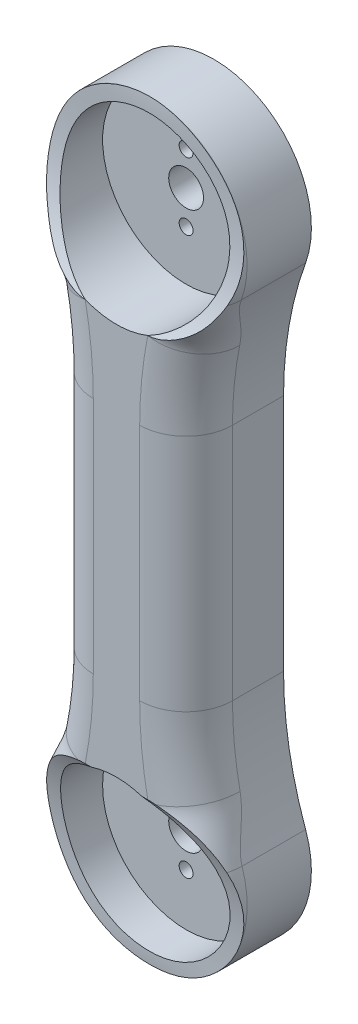
SolidWorks part; units mm, degrees
ref_plane "Front Plane" through (0, 0, 0) normal (0, 0, 1) x (1, 0, 0)
ref_plane "Top Plane" through (0, 0, 0) normal (0, 1, 0) x (1, 0, 0)
ref_plane "Right Plane" through (0, 0, 0) normal (1, 0, 0) x (0, 0, -1)
sketch "Sketch9" plane through (0, 0, 0) normal (0, 0, 1) x (1, 0, 0)
  line L0 (-9.4143, 0.3919) -> (-9.4143, 5.0677) construction
  line L1 (-28.6016, 137.3176) -> (-28.5046, 137.3176) construction
  line L2 (-24.4143, 111.7748) -> (-24.4143, 60.3605)
  line L3 (5.5857, 111.7748) -> (5.5857, 60.3605)
  circle A0 centre (-9.4143, 153.3177) radius 1.5
  circle A1 centre (-9.4143, 146.0677) radius 3.7501
  circle A2 centre (-9.4143, 138.8176) radius 1.5
  arc A3 (10.3381, 138.9375) -> (-29.1668, 138.9375) centre (-9.4143, 146.0677) ccw
  circle A4 centre (-9.4143, 18.8177) radius 1.5
  circle A5 centre (-9.4143, 26.0677) radius 3.7501
  circle A6 centre (-9.4143, 33.3177) radius 1.5
  arc A7 (10.3381, 33.1979) -> (-29.1668, 33.1979) centre (-9.4143, 26.0677) cw
  arc A8 (-29.1668, 33.1979) -> (-24.4143, 60.3605) centre (-104.4143, 60.3605) ccw
  arc A9 (5.5857, 60.3605) -> (10.3381, 33.1979) centre (85.5857, 60.3605) ccw
  arc A10 (5.5857, 111.7748) -> (10.3381, 138.9375) centre (85.5857, 111.7748) cw
  arc A11 (-29.1668, 138.9375) -> (-24.4143, 111.7748) centre (-104.4143, 111.7748) cw
  point P13 (-9.4143, 86.0677)
  point P14 (-9.4143, 86.9252)
extrude "Boss-Extrude2" add sketch "Sketch9" along normal blind 21 separate body
sketch "Sketch12" plane through (0, 0, 21) normal (0, 0, 1) x (1, 0, 0)
  line L0 (120.7444, 166.8402) -> (120.7444, 163.8342) construction
  line L1 (-24.895, 85.8401) -> (5.105, 85.8401) construction
  line L2 (-9.4143, 149.8177) -> (-9.4143, 142.3176) construction
  circle A0 centre (-9.4143, 146.0677) radius 17.994
  circle A1 centre (-9.4143, 25.6126) radius 17.994
  circle A2 centre (-9.4143, 146.0677) radius 3.7501 construction
extrude "Cut-Extrude6" cut sketch "Sketch12" against normal blind 15
fillet "Fillet2" radius 10 6 edges at (-25.6114, 125.5625, 21) (6.7827, 125.5625, 21) (5.5857, 86.0677, 21) (6.7827, 46.5729, 21) (-25.6114, 46.5729, 21) (-24.4143, 86.0677, 21)
sketch "Sketch14" plane through (0, 0, 0) normal (1, 0, 0) x (0, 0, -1)
  line L0 (-21, 8.0737) -> (-21, 7.6186)
  line L1 (-14.3283, 5.0677) -> (-13.8527, 5.0677)
  line L6 (-21, 164.0617) -> (-21, 139.9581) construction
  line L7 (-21, 164.0617) -> (-21, 139.9581)
  line L8 (-21, 129.3834) -> (-21, 139.9581) construction
  line L10 (-21, 129.3834) -> (-21, 139.9581)
  line L11 (-21, 42.7519) -> (-21, 32.1772)
  line L12 (-21, 8.0737) -> (-21, 32.1772)
  arc A0 (-13.8527, 167.0677) -> (-21, 164.0617) centre (-13.8527, 157.0677) ccw construction
  arc A1 (-13.8527, 167.0677) -> (-21, 164.0617) centre (-13.8527, 157.0677) ccw
  spline S0 degree 3 poles (-21, 129.3834) (-11.4926, 144.9136) (-14.5345, 159.5534) (-13.8527, 167.0677) knots 0 0 0 0 1 1 1 1
  spline S1 degree 3 poles (-21, 42.7519) (-11.4926, 27.2218) (-14.5345, 12.5819) (-13.8527, 5.0677) knots 0 0 0 0 1 1 1 1
  spline S2 degree 3 poles (-14.3283, 5.0677) (-16.8187, 5.0677) (-19.1449, 5.9571) (-21, 7.6186) knots 0 0 0 0 1 1 1 1 weights 1 0.956034 0.956034 1 construction
  spline S3 degree 3 poles (-14.3283, 5.0677) (-16.8187, 5.0677) (-19.1449, 5.9571) (-21, 7.6186) knots 0 0 0 0 1 1 1 1 weights 1 0.956034 0.956034 1
extrude "Cut-Extrude7" cut sketch "Sketch14" against normal through all both and the other way through all
